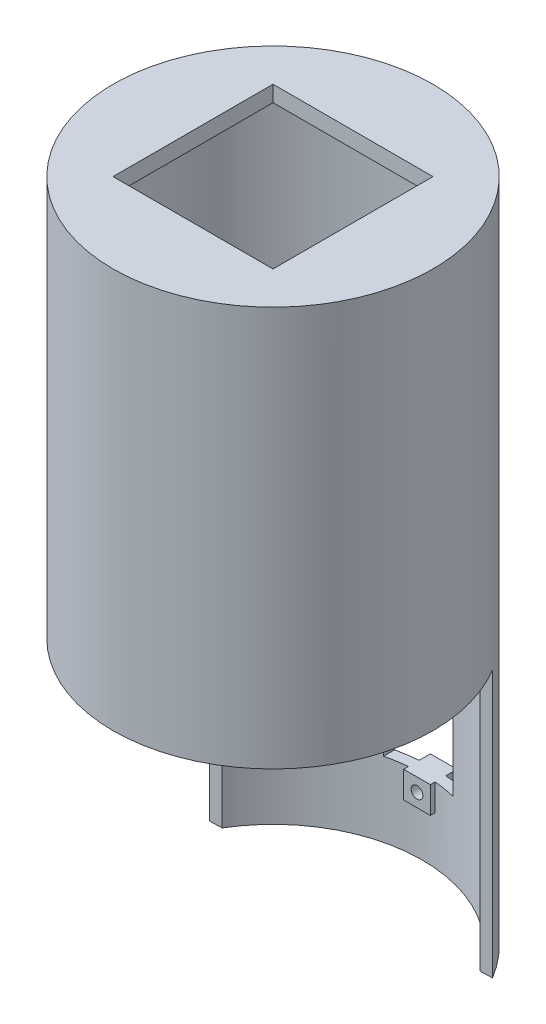
SolidWorks part; units mm, degrees
ref_plane "前基準面" through (0, 0, 0) normal (0, 0, 1) x (1, 0, 0)
ref_plane "上基準面" through (0, 0, 0) normal (0, 1, 0) x (1, 0, 0)
ref_plane "右基準面" through (0, 0, 0) normal (1, 0, 0) x (0, 0, -1)
sketch "草圖1" plane through (0, 0, 0) normal (0, 1, 0) x (1, 0, 0)
  circle A0 centre (0, 0) radius 30
  circle A1 centre (0, 0) radius 29
  dimension "D1" = 60
  dimension "D2" = 58
extrude "填料-伸長1" add sketch "草圖1" along normal blind 75 and the other way blind 50 contours A0
ref_plane "平面3" through (0, -10, 0) normal (0, 1, 0) x (1, 0, 0)
sketch "草圖8" plane through (0, 0, 0) normal (0, 1, 0) x (1, 0, 0)
  line L0 (0, 30) -> (0, -30) construction
  line L1 (14, 20.8205) -> (-14, 20.8205)
  line L2 (-14, 20.8205) -> (-14, -20.1795)
  line L3 (-14, -20.1795) -> (14, -20.1795)
  line L4 (14, 20.8205) -> (14, -20.1795)
  circle A1 centre (0, 0) radius 30 construction
  point P11 (0, -20.1795)
  point P12 (0, 20.8205)
  dimension "D1" = 28
  dimension "D2" = 41
sketch "草圖10" plane through (0, 75, 0) normal (0, 1, 0) x (1, 0, 0)
  line L0 (0, 30) -> (0, -30) construction
  line L10 (-30, 0) -> (30, 0) construction
  line L11 (-33, 0) -> (33, 0) construction
  line L12 (-15, 15) -> (-15, -15)
  line L13 (-15, 15) -> (15, 15)
  line L15 (-15, -15) -> (15, -15)
  line L16 (15, 15) -> (15, -15)
  circle A0 centre (0, 0) radius 30 construction
  dimension "D1" = 15
  dimension "D2" = 30
extrude "除料-伸長8" cut sketch "草圖10" against normal blind 45.1
ref_plane "平面4" through (0, 0, -37) normal (0, 0, 1) x (1, 0, 0)
extrude "除料-伸長9" cut sketch "草圖10<2>" against normal blind 113 and the other way blind 10
sketch "草圖10<2>" plane through (0, 75, 0) normal (0, 1, 0) x (1, 0, 0) same geometry as "草圖10"
sketch "草圖11" plane through (0, 0, 0) normal (0, 1, 0) x (1, 0, 0)
  line L0 (25.7323, 15.4223) -> (-26.3259, 14.3857)
  circle A1 centre (0, 0) radius 30 construction
  arc A3 (-26.3259, 14.3857) -> (25.7323, 15.4223) centre (0, 0) ccw
extrude "除料-伸長10" cut sketch "草圖11" against normal blind 54
sketch "草圖12" plane through (0, 0, 0) normal (0, 1, 0) x (1, 0, 0)
  line L0 (0, 30) -> (0, -30) construction
  circle A0 centre (0, 0) radius 28
  dimension "D1" = 56
extrude "除料-伸長11" cut sketch "草圖12" against normal blind 55 and the other way blind 72
sketch "草圖13" plane through (0, 0, 0) normal (0, 0, 1) x (1, 0, 0)
  line L0 (0, 0) -> (0, -54.6017) construction
  line L1 (-26.3259, -25) -> (23.4005, -25) construction
  line L2 (-26.3259, -50) -> (-26.3259, 0) construction
  line L3 (23.4005, -50) -> (23.4005, 0) construction
  line L5 (-6.5, -12.5) -> (6.5, -12.5)
  line L6 (-6.5, -12.5) -> (-6.5, -36)
  line L7 (-6.5, -36) -> (6.5, -36)
  line L8 (6.5, -12.5) -> (6.5, -36)
  dimension "D1" = 13
  dimension "D2" = 23.5
  dimension "D3" = 6.5
  dimension "D4" = 12.5
extrude "除料-伸長12" cut sketch "草圖13" against normal blind 54
ref_plane "平面5" through (0, 0, -28) normal (0, 0, 1) x (1, 0, 0)
sketch "草圖14" plane through (0, 0, -28) normal (0, 0, 1) x (1, 0, 0)
  line L0 (0, -12.5) -> (0, -38.2336) construction
  line L1 (-6.5, -12.5) -> (6.5, -12.5) construction
  line L7 (6.5, -24.25) -> (-6.5, -24.25) construction
  line L8 (6.5, -12.5) -> (6.5, -36) construction
  line L9 (-6.5, -36) -> (-6.5, -12.5) construction
  line L10 (2.5, -36) -> (-2.5, -36)
  line L11 (2.5, -7.5) -> (-2.5, -7.5)
  line L12 (2.5, -7.5) -> (2.5, -12.5)
  line L13 (2.5, -12.5) -> (-2.5, -12.5)
  line L14 (-2.5, -7.5) -> (-2.5, -12.5)
  line L15 (-2.5, -41) -> (-2.5, -36)
  line L16 (2.5, -41) -> (-2.5, -41)
  line L17 (2.5, -41) -> (2.5, -36)
  dimension "D1" = 5
  dimension "D2" = 5
  dimension "D3" = 2.5
extrude "填料-伸長2" add sketch "草圖14" against normal blind 4 and the other way blind 1
sketch "草圖15" plane through (0, 0, -28) normal (0, 0, 1) x (1, 0, 0)
  line L0 (6.5, -24.25) -> (-6.5, -24.25) construction
  line L3 (6.5, -12.5) -> (6.5, -36) construction
  line L4 (-6.5, -36) -> (-6.5, -12.5) construction
  line L5 (33, -10) -> (-33, -10) construction
  circle A2 centre (0, -10) radius 1.1
  circle A3 centre (0, -38.5) radius 1.1
  dimension "D1" = 2.2
extrude "除料-伸長13" cut sketch "草圖15" against normal blind 5 and the other way blind 4
